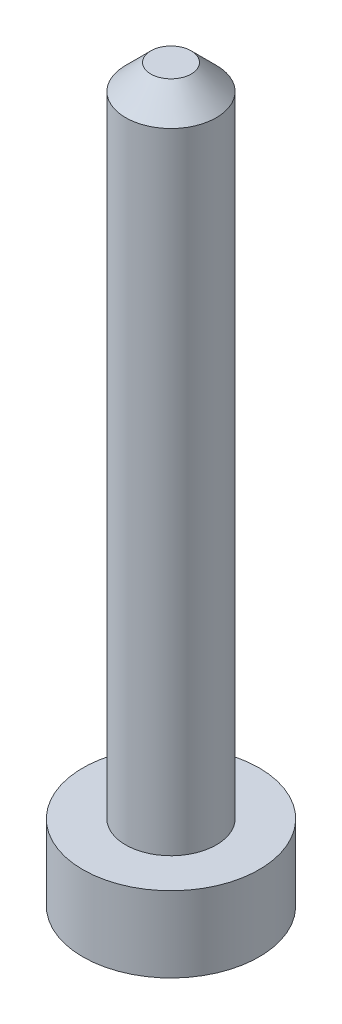
SolidWorks part; units mm, degrees
ref_plane "Спереди" through (0, 0, 0) normal (0, 0, 1) x (1, 0, 0)
ref_plane "Сверху" through (0, 0, 0) normal (0, 1, 0) x (1, 0, 0)
ref_plane "Справа" through (0, 0, 0) normal (1, 0, 0) x (0, 0, -1)
sketch "Эскиз1" plane through (0, 0, 0) normal (0, 1, 0) x (1, 0, 0)
  circle A0 centre (0, 0) radius 3.5
  circle A1 centre (0, 0) radius 1.8
  dimension "D1" = 7
  dimension "D2" = 3.6
extrude "Бобышка-Вытянуть1" add sketch "Эскиз1" against normal blind 3 contours A1 | A0 A1 region at (-3.401, 0, 0) region at (0, 0, 0)
extrude "Бобышка-Вытянуть2" add sketch "Эскиз1<3>" along normal blind 26 contours A1 region at (0, 0, 0)
sketch "Эскиз1<3>" plane through (0, 0, 0) normal (0, 1, 0) x (1, 0, 0) same geometry as "Эскиз1"
chamfer "Фаска1" distance 1 angle 45 1 edges at (0, 26, 1.8)
